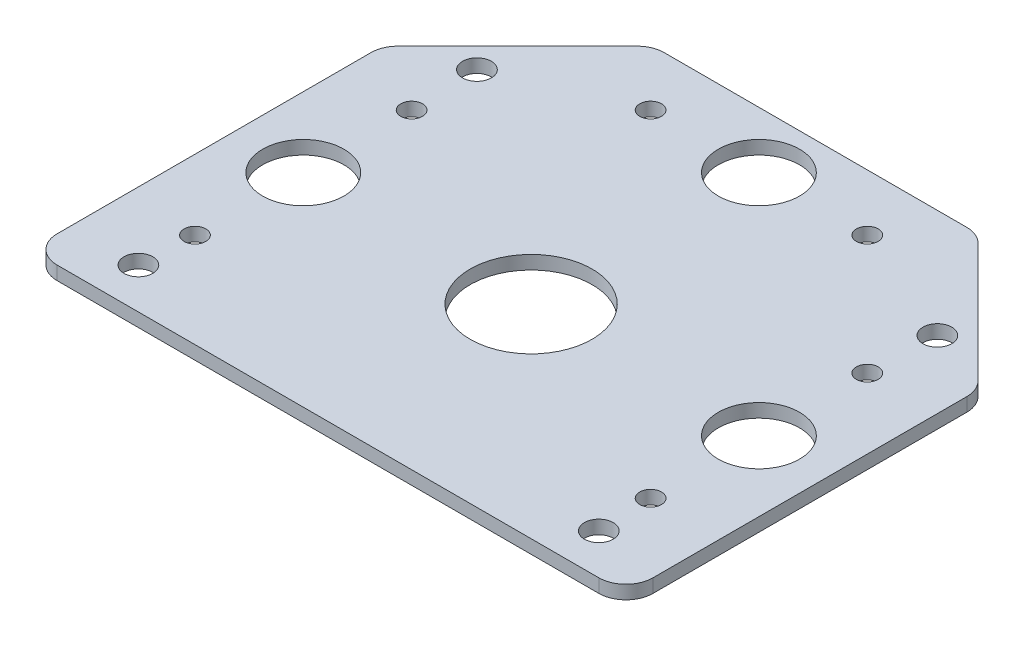
SolidWorks part; units mm, degrees
material "6061 Alloy"
ref_plane "Front Plane" through (0, 0, 0) normal (0, 0, 1) x (1, 0, 0)
ref_plane "Top Plane" through (0, 0, 0) normal (0, 1, 0) x (1, 0, 0)
ref_plane "Right Plane" through (0, 0, 0) normal (1, 0, 0) x (0, 0, -1)
sketch "Sketch1" plane through (0, 0, 0) normal (0, 1, 0) x (1, 0, 0)
  line L7 (-69.85, -57.15) -> (69.85, -57.15)
  line L8 (-69.85, -57.15) -> (-69.85, 57.15)
  line L9 (-69.85, 57.15) -> (69.85, 57.15)
  line L10 (69.85, -57.15) -> (69.85, 57.15)
  line L11 (-69.85, -57.15) -> (69.85, 57.15) construction
  line L12 (-69.85, 57.15) -> (69.85, -57.15) construction
  circle A2 centre (0, 43.8912) radius 9.525
  circle A3 centre (-53.4162, -9.525) radius 9.525
  circle A4 centre (53.4162, -9.525) radius 9.525
  circle A5 centre (0, -9.525) radius 14.2875
  circle A6 centre (0, -9.525) radius 53.4162 construction
  point P0 (0, 0)
  dimension "D3" = 28.575
  dimension "D4" = 9.525
  dimension "D5" = 19.05
  dimension "D6" = 19.05
  dimension "D7" = 19.05
  dimension "D8" = 106.8324
  dimension "D1" = 139.7
  dimension "D2" = 114.3
extrude "Boss-Extrude1" add sketch "Sketch1" along normal mid plane 3.175
hole_wizard "#10 Clearance Hole1" positions "Sketch3" profile "Sketch4" hole size "#10" standard "ANSI Inch" end condition up to next
sketch "Sketch3" plane through (0, 1.5875, 0) normal (0, 1, 0) x (1, 0, 0)
  circle A0 centre (53.4162, -9.525) radius 9.525 construction
  circle A1 centre (0, 43.8912) radius 9.525 construction
  circle A2 centre (-53.4162, -9.525) radius 9.525 construction
  circle A3 centre (53.4162, -9.525) radius 9.525
  circle A4 centre (0, 43.8912) radius 9.525
  circle A5 centre (-53.4162, -9.525) radius 9.525
  circle A6 centre (-53.4162, -9.525) radius 25.4 construction
  circle A7 centre (0, 43.8912) radius 25.4 construction
  circle A8 centre (53.4162, -9.525) radius 25.4 construction
  point P0 (-53.4162, 15.875)
  point P16 (-53.4162, -34.925)
  point P22 (-25.4, 43.8912)
  point P24 (25.4, 43.8912)
  point P29 (53.4162, 15.875)
  point P31 (53.4162, -34.925)
  dimension "D1" = 50.8
  dimension "D2" = 50.8
  dimension "D3" = 50.8
sketch "Sketch4" plane through (-53.4162, 1.5875, -15.875) normal (1, 0, 0) x (0, 0, 1)
  line L0 (0, 0) -> (0, 3.175)
  line L1 (0, 3.175) -> (2.5527, 3.175)
  line L2 (2.5527, 3.175) -> (2.5527, 0)
  line L5 (2.5527, 0) -> (0, 0)
  line L11 (0, -6.35) -> (0, 107.95) construction
  dimension "Thru Hole Dia." = 5.1054
  dimension "Thru Hole Depth" = 3.175
hole_wizard "1/4 Clearance Hole1" positions "Sketch5" profile "Sketch6" hole size "1/4" standard "ANSI Inch" end condition up to next
sketch "Sketch5" plane through (0, 1.5875, 0) normal (0, 1, 0) x (1, 0, 0)
  circle A0 centre (0, -9.525) radius 14.2875 construction
  circle A1 centre (0, -9.525) radius 14.2875
  point P0 (-53.975, 31.75)
  point P13 (53.975, 31.75)
  point P15 (-53.975, -47.625)
  point P17 (53.975, -47.625)
  dimension "D1" = 53.975
  dimension "D2" = 41.275
  dimension "D3" = 38.1
  dimension "D4" = 53.975
sketch "Sketch6" plane through (-53.975, 1.5875, -31.75) normal (1, 0, 0) x (0, 0, 1)
  line L0 (0, 0) -> (0, 3.175)
  line L1 (0, 3.175) -> (3.3782, 3.175)
  line L2 (3.3782, 3.175) -> (3.3782, 0)
  line L5 (3.3782, 0) -> (0, 0)
  line L11 (0, -6.35) -> (0, 107.95) construction
  dimension "Thru Hole Dia." = 6.7564
  dimension "Thru Hole Depth" = 3.175
chamfer "Chamfer1" distance 31.75 angle 45 2 edges at (69.85, 0, -57.15) (-69.85, 0, -57.15)
fillet "Fillet2" radius 6.35 6 edges at (-69.85, 0, 57.15) (69.85, 0, 57.15) (69.85, 0, -25.4) (38.1, 0, -57.15) (-38.1, 0, -57.15) (-69.85, 0, -25.4)
